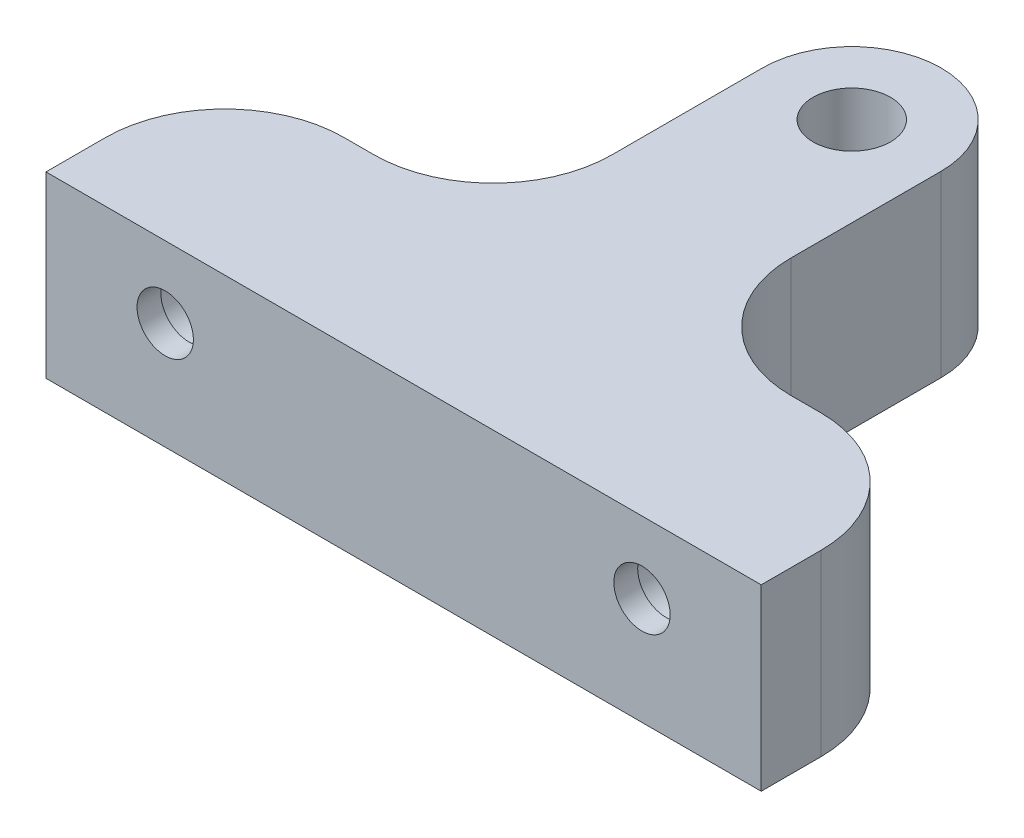
SolidWorks part; units mm, degrees
ref_plane "Front Plane" through (0, 0, 0) normal (0, 0, 1) x (1, 0, 0)
ref_plane "Top Plane" through (0, 0, 0) normal (0, 1, 0) x (1, 0, 0)
ref_plane "Right Plane" through (0, 0, 0) normal (1, 0, 0) x (0, 0, -1)
sketch "Sketch1" plane through (0, 0, 0) normal (0, 1, 0) x (1, 0, 0)
  line L0 (38.1, 0) -> (38.1, 50000) construction
  line L1 (0, 0) -> (76.2, 0)
  line L5 (0, 47.752) -> (28.575, 47.752) construction
  line L6 (15.875, 19.05) -> (12.7, 19.05)
  line L8 (28.575, 47.752) -> (28.575, 31.75)
  line L9 (41.275, 0) -> (60.325, 0)
  line L10 (47.625, 47.752) -> (47.625, 31.75)
  line L11 (76.2, 0) -> (0, 0)
  line L12 (76.2, 0) -> (76.2, 6.35)
  line L13 (63.5, 19.05) -> (60.325, 19.05)
  line L14 (0, 0) -> (0, 6.35)
  line L15 (12.7, -8.9527) -> (12.7, 49991.0473) construction
  line L16 (63.5, -16.9436) -> (63.5, 49983.0564) construction
  line L17 (60.75, -9.3967) -> (60.75, 49990.6033) construction
  line L18 (15.45, -9.5446) -> (15.45, 49990.4554) construction
  line L19 (66.25, -20.1991) -> (66.25, 49979.8009) construction
  line L20 (9.95, -29.6698) -> (9.95, 49970.3302) construction
  line L21 (47.625, 47.752) -> (50000, 47.752) construction
  circle A0 centre (38.1, 47.752) radius 4.125
  arc A1 (47.625, 47.752) -> (28.575, 47.752) centre (38.1, 47.752) ccw
  arc A2 (0, 6.35) -> (12.7, 19.05) centre (12.7, 6.35) cw
  arc A3 (76.2, 6.35) -> (63.5, 19.05) centre (63.5, 6.35) ccw
  arc A4 (15.875, 19.05) -> (28.575, 31.75) centre (15.875, 31.75) ccw
  arc A5 (60.325, 19.05) -> (47.625, 31.75) centre (60.325, 31.75) cw
  point P7 (38.1, 0)
  dimension "D4" = 8.25
  dimension "D5" = 19.05
  dimension "D11" = 12.7
  dimension "D1" = 76.2
  dimension "D2" = 25.4
  dimension "D3" = 47.752
  dimension "D6" = 25.4
  dimension "D7" = 2.75
  dimension "D8" = 2.75
  dimension "D9" = 2.75
  dimension "D10" = 2.75
extrude "Boss-Extrude1" add sketch "Sketch1" against normal blind 19.05 contours L13 A5 L10 A1 L8 A4 L6 A2 L14 L1 L12 A3 A0 region at (38.1, 0, -17.874)
sketch "Sketch2" plane through (0, 0, -19.05) normal (0, 0, -1) x (-1, 0, 0)
  line L0 (-88.9, -7.62) -> (49911.1, -7.62) construction
  line L2 (-38.1, 0) -> (-38.1, -50000) construction
  line L3 (-28.575, 0) -> (-47.625, 0) construction
  line L4 (-47.625, -19.05) -> (-28.575, -19.05) construction
  line L5 (-63.5, 0) -> (-63.5, -50000) construction
  line L8 (-12.7, 0) -> (-12.7, -50000) construction
  line L10 (-15.875, 0) -> (-12.7, 0) construction
  circle A0 centre (-63.5, -7.62) radius 3
  circle A1 centre (-12.7, -7.62) radius 3
  point P6 (-38.1, 0)
  point P9 (-38.1, -19.05)
  dimension "D4" = 6
  dimension "D5" = 6
  dimension "D1" = 25.4
  dimension "D2" = 25.4
  dimension "D3" = 7.62
extrude "Cut-Extrude1" cut sketch "Sketch2" against normal blind 19.05
sketch "Sketch3" plane through (0, 0, -19.05) normal (0, 0, -1) x (-1, 0, 0)
  circle A0 centre (-63.5, -7.62) radius 3.44
  circle A1 centre (-12.7, -7.62) radius 3.44
  dimension "D1" = 6.88
  dimension "D2" = 6.88
extrude "Cut-Extrude2" cut sketch "Sketch3" against normal blind 16.51 and the other way blind 16.51
